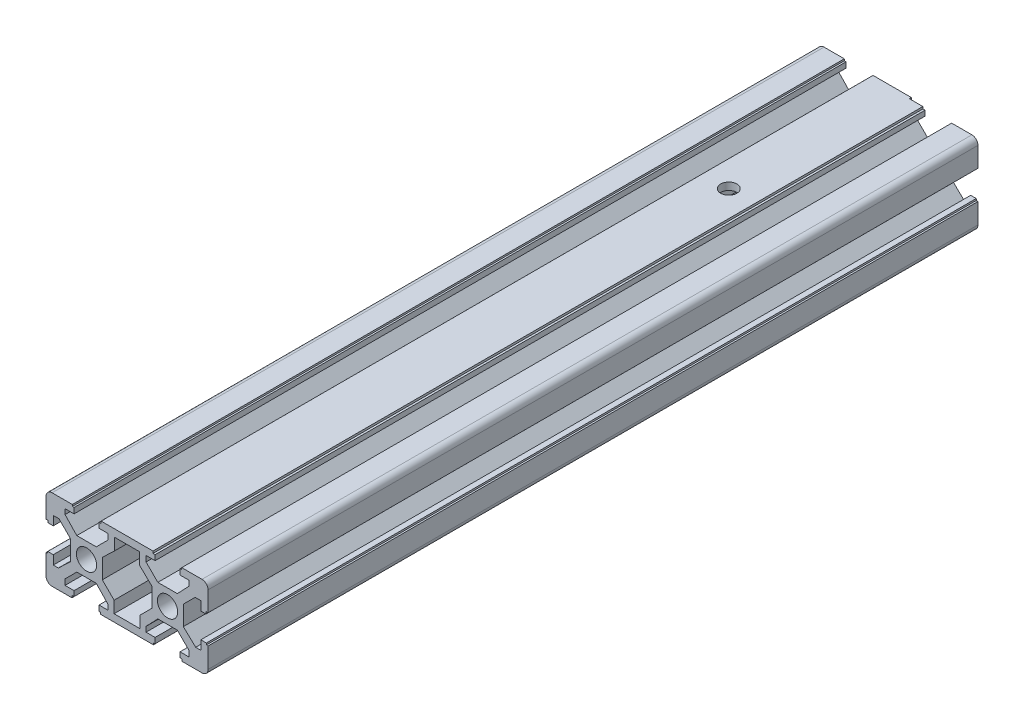
SolidWorks part; units mm, degrees
ref_plane "Front Plane" through (0, 0, 0) normal (0, 0, 1) x (1, 0, 0)
ref_plane "Top Plane" through (0, 0, 0) normal (0, 1, 0) x (1, 0, 0)
ref_plane "Right Plane" through (0, 0, 0) normal (1, 0, 0) x (0, 0, -1)
sketch "Sketch1" plane through (0, 0, 0) normal (0, 0, 1) x (1, 0, 0)
  line L0 (-3.0596, 5.3047) -> (-3.0596, 8.2)
  line L1 (-3.0596, 8.2) -> (0, 8.2)
  line L2 (-6.1, 0) -> (6.1, 0) construction
  line L4 (-1.5, 10) -> (0, 10)
  line L5 (-20, -3.4975) -> (-20, -10)
  line L6 (-18.5, -10) -> (-13.6, -10)
  line L7 (-6.1, 2.4047) -> (-3.0596, 5.3047)
  line L10 (-3.2, -5.3047) -> (-3.2, -8.2)
  line L11 (-3.2, -8.2) -> (0, -8.2)
  line L13 (-6.1, -2.4047) -> (-3.2, -5.3047)
  line L14 (-6.1, -2.4047) -> (-6.1, 2.4047)
  line L15 (-6.5025, -9.5731) -> (-6.5025, -10)
  line L16 (-6.925, -9.5658) -> (-6.5025, -9.5731)
  line L17 (-6.925, -8.2) -> (-6.925, -9.5658)
  line L18 (-4.6953, -8.2) -> (-6.925, -8.2)
  line L19 (-4.6953, -8.2) -> (-4.6953, -6.9404)
  line L20 (-6.5025, -10) -> (-1.6025, -10)
  line L21 (0, -10) -> (-1.6025, -10)
  line L22 (-7.5953, -3.9) -> (-4.6953, -6.9404)
  line L23 (-13.6, -9.4791) -> (-13.6, -10)
  line L24 (-13.075, -9.4791) -> (-13.6, -9.4791)
  line L25 (-13.075, -8.2) -> (-13.075, -9.4791)
  line L26 (-15.3047, -8.2) -> (-13.075, -8.2)
  line L27 (-15.3047, -8.2) -> (-15.3047, -6.8)
  line L28 (-12.4047, -3.9) -> (-15.3047, -6.8)
  line L29 (-12.4047, -3.9) -> (-7.5953, -3.9)
  line L30 (-19.5731, -3.4975) -> (-20, -3.4975)
  line L31 (-19.5658, -3.075) -> (-19.5731, -3.4975)
  line L32 (-18.2, -3.075) -> (-19.5658, -3.075)
  line L33 (-18.2, -5.3047) -> (-18.2, -3.075)
  line L34 (-18.2, -5.3047) -> (-16.9404, -5.3047)
  line L35 (0, 8.2) -> (3.0596, 8.2)
  line L36 (-1.5, 10) -> (-6.4, 10)
  line L37 (-13.9, -2.4047) -> (-16.9404, -5.3047)
  line L38 (-19.4791, 3.6) -> (-20, 3.6)
  line L39 (-19.4791, 3.075) -> (-19.4791, 3.6)
  line L40 (-18.2, 3.075) -> (-19.4791, 3.075)
  line L41 (-18.2, 5.3047) -> (-18.2, 3.075)
  line L42 (-18.2, 5.3047) -> (-16.8, 5.3047)
  line L43 (-13.9, 2.4047) -> (-16.8, 5.3047)
  line L44 (-13.9, 2.4047) -> (-13.9, -2.4047)
  line L45 (-12.4047, 3.9) -> (-15.3047, 6.9404)
  line L47 (-15.3047, 8.2) -> (-15.3047, 6.9404)
  line L48 (-7.5953, 3.9) -> (-4.6953, 6.8)
  line L49 (-4.6953, 8.2) -> (-4.6953, 6.8)
  line L50 (-20, 3.6) -> (-20, 10)
  line L51 (-13.4975, 10) -> (-20, 10)
  line L52 (-18.5, -10) -> (-1.6025, -10) construction
  line L53 (20, 8.5035) -> (20, 10) construction
  line L54 (3.0596, 5.3047) -> (3.0596, 8.2)
  line L55 (-20, -10) -> (0, 10) construction
  line L56 (-20, 10) -> (0, -10) construction
  line L60 (-10, 0) -> (-13.9, 0) construction
  line L61 (-10, 0) -> (-10, 3.9) construction
  line L62 (-10, 0) -> (-6.1, 0) construction
  line L63 (-13, 6.4) -> (-7, 6.4) construction
  line L64 (-13, 6.4) -> (-13, 4.9) construction
  line L65 (-13, 4.9) -> (-7, 4.9) construction
  line L66 (-6.4, 9.4791) -> (-6.4, 10)
  line L67 (-6.925, 9.4791) -> (-6.4, 9.4791)
  line L68 (-6.925, 8.2) -> (-6.925, 9.4791)
  line L69 (-10, 0) -> (-10, -3.9) construction
  line L70 (-4.6953, 8.2) -> (-6.925, 8.2)
  line L76 (-7, 6.4) -> (-7, 4.9) construction
  line L77 (-13, 6.4) -> (-7, 4.9) construction
  line L78 (-13, 4.9) -> (-7, 6.4) construction
  line L86 (-7.5953, 3.9) -> (-12.4047, 3.9)
  line L88 (-15.3047, 8.2) -> (-13.075, 8.2)
  line L89 (-13.075, 8.2) -> (-13.075, 9.5658)
  line L90 (-13.075, 9.5658) -> (-13.4975, 9.5731)
  line L91 (-13.4975, 9.5731) -> (-13.4975, 10)
  line L106 (0, -10) -> (1.6025, -10)
  line L107 (0, 10) -> (1.5, 10)
  line L108 (18.5, -10) -> (20, -10)
  line L109 (20, -8.3975) -> (20, -10)
  line L112 (18.3975, 10) -> (20, 10)
  line L113 (20, 8.5035) -> (20, 10)
  line L114 (-20, -3.4975) -> (-20, 3.6) construction
  line L115 (-18.5, -10) -> (-20, -10)
  line L132 (1.6025, -10) -> (18.5, -10) construction
  line L133 (0, -8.2) -> (3.2, -8.2)
  line L134 (3.2, -5.3047) -> (3.2, -8.2)
  line L137 (13, 4.9) -> (7, 6.4) construction
  line L138 (13, 6.4) -> (7, 4.9) construction
  line L139 (7, 6.4) -> (7, 4.9) construction
  line L140 (10, 0) -> (10, -3.9) construction
  line L141 (13, 4.9) -> (7, 4.9) construction
  line L142 (13, 6.4) -> (13, 4.9) construction
  line L143 (13, 6.4) -> (7, 6.4) construction
  line L144 (10, 0) -> (6.1, 0) construction
  line L145 (10, 0) -> (10, 3.9) construction
  line L146 (10, 0) -> (13.9, 0) construction
  line L147 (20, 10) -> (0, -10) construction
  line L148 (20, -10) -> (0, 10) construction
  line L149 (20, -8.3975) -> (20, 8.5) construction
  line L150 (13.4975, 9.5731) -> (13.4975, 10)
  line L151 (13.075, 9.5658) -> (13.4975, 9.5731)
  line L152 (13.075, 8.2) -> (13.075, 9.5658)
  line L153 (15.3047, 8.2) -> (13.075, 8.2)
  line L154 (7.5953, 3.9) -> (12.4047, 3.9)
  line L155 (4.6953, 8.2) -> (6.925, 8.2)
  line L156 (6.925, 8.2) -> (6.925, 9.4791)
  line L157 (6.925, 9.4791) -> (6.4, 9.4791)
  line L158 (6.4, 9.4791) -> (6.4, 10)
  line L159 (20, 8.5) -> (20, 3.6)
  line L160 (13.4975, 10) -> (18.3975, 10)
  line L161 (4.6953, 8.2) -> (4.6953, 6.8)
  line L162 (7.5953, 3.9) -> (4.6953, 6.8)
  line L163 (15.3047, 8.2) -> (15.3047, 6.9404)
  line L164 (12.4047, 3.9) -> (15.3047, 6.9404)
  line L165 (13.9, 2.4047) -> (13.9, -2.4047)
  line L166 (13.9, 2.4047) -> (16.8, 5.3047)
  line L167 (18.2, 5.3047) -> (16.8, 5.3047)
  line L168 (18.2, 5.3047) -> (18.2, 3.075)
  line L169 (18.2, 3.075) -> (19.4791, 3.075)
  line L170 (19.4791, 3.075) -> (19.4791, 3.6)
  line L171 (19.4791, 3.6) -> (20, 3.6)
  line L172 (13.9, -2.4047) -> (16.9404, -5.3047)
  line L173 (1.5, 10) -> (6.4, 10)
  line L174 (18.2, -5.3047) -> (16.9404, -5.3047)
  line L175 (18.2, -5.3047) -> (18.2, -3.075)
  line L176 (18.2, -3.075) -> (19.5658, -3.075)
  line L177 (19.5658, -3.075) -> (19.5731, -3.4975)
  line L178 (19.5731, -3.4975) -> (20, -3.4975)
  line L179 (12.4047, -3.9) -> (7.5953, -3.9)
  line L180 (12.4047, -3.9) -> (15.3047, -6.8)
  line L181 (15.3047, -8.2) -> (15.3047, -6.8)
  line L182 (15.3047, -8.2) -> (13.075, -8.2)
  line L183 (13.075, -8.2) -> (13.075, -9.4791)
  line L184 (13.075, -9.4791) -> (13.6, -9.4791)
  line L185 (13.6, -9.4791) -> (13.6, -10)
  line L186 (7.5953, -3.9) -> (4.6953, -6.9404)
  line L187 (6.5025, -10) -> (1.6025, -10)
  line L188 (4.6953, -8.2) -> (4.6953, -6.9404)
  line L189 (4.6953, -8.2) -> (6.925, -8.2)
  line L190 (6.925, -8.2) -> (6.925, -9.5658)
  line L191 (6.925, -9.5658) -> (6.5025, -9.5731)
  line L192 (6.5025, -9.5731) -> (6.5025, -10)
  line L193 (6.1, -2.4047) -> (6.1, 2.4047)
  line L194 (6.1, -2.4047) -> (3.2, -5.3047)
  line L195 (6.1, 2.4047) -> (3.0596, 5.3047)
  line L196 (18.5, -10) -> (13.6, -10)
  line L197 (20, -3.4975) -> (20, -8.3975)
  line L198 (0, 10) -> (0, -10) construction
  line L199 (20, 8.5035) -> (20, 8.5)
  circle A0 centre (-10, 0) radius 2.5
  circle A1 centre (10, 0) radius 2.5
  point P57 (-10, 0)
  point P63 (-10, 0)
  dimension "D1" = 6
  dimension "D2" = 1.5
  dimension "D3" = 3.075
  dimension "D4" = 3.075
  dimension "D5" = 3.075
  dimension "D6" = 20
  dimension "D7" = 20
  dimension "D8" = 40
extrude "Boss-Extrude1" add sketch "Sketch1" against normal blind 190.5
fillet "Fillet1" radius 1.5 4 edges at (-20, -10, -95.25) (-20, 10, -95.25) (20, -10, -95.25) (20, 10, -95.25)
ref_plane "Plane1" through (10, 0, 0) normal (1, 0, 0) x (0, 0, -1)
ref_plane "Plane2" through (-10, 0, 0) normal (1, 0, 0) x (0, 0, -1)
sketch "Sketch2" plane through (0, 10, 0) normal (0, 1, 0) x (1, 0, 0)
  line L0 (6.4, 190.5) -> (-6.4, 190.5) construction
  line L1 (3.0596, 190.5) -> (20, 190.5)
  line L2 (3.0596, 190.5) -> (3.0596, 190)
  line L3 (3.0596, 190) -> (20, 190)
  line L4 (20, 190.5) -> (20, 190)
  line L5 (20, 190.5) -> (20, 0) construction
  line L6 (3.0596, 190.5) -> (3.0596, 0) construction
extrude "Cut-Extrude1" cut sketch "Sketch2" against normal blind 23
sketch "Sketch3" plane through (0, -10, 0) normal (0, -1, 0) x (1, 0, 0)
  line L0 (6.5025, -148.5) -> (-6.5025, -148.5) construction
  line L1 (6.5025, -190) -> (6.5025, 0) construction
  line L2 (-6.5025, -190.5) -> (-6.5025, 0) construction
  line L3 (-18.5, -190.5) -> (-13.6, -190.5) construction
  circle A0 centre (0, -148.5) radius 2
  dimension "D1" = 42
extrude "Cut-Extrude2" cut sketch "Sketch3" against normal blind 23
